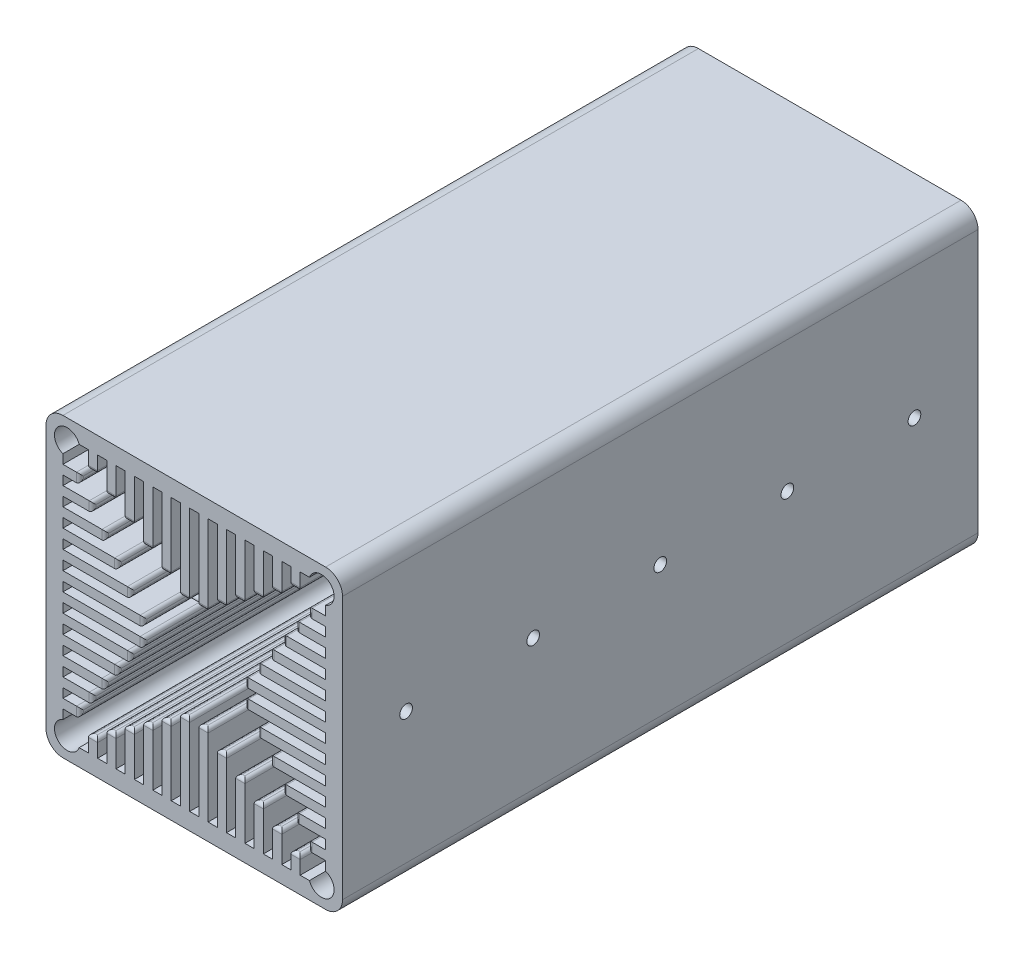
SolidWorks part; units mm, degrees
ref_plane "Front Plane" through (0, 0, 0) normal (0, 0, 1) x (1, 0, 0)
ref_plane "Top Plane" through (0, 0, 0) normal (0, 1, 0) x (1, 0, 0)
ref_plane "Right Plane" through (0, 0, 0) normal (1, 0, 0) x (0, 0, -1)
sketch "Sketch1" plane through (0, 0, 0) normal (0, 0, 1) x (1, 0, 0)
  line L1 (0, 0) -> (70, 0)
  line L2 (0, 0) -> (0, -70)
  line L3 (0, -70) -> (70, -70)
  line L4 (70, 0) -> (70, -70)
  dimension "D1" = 70
  dimension "D2" = 70
extrude "Boss-Extrude1" add sketch "Sketch1" along normal blind 150
fillet "Fillet1" radius 4 4 edges at (0, -70, 75) (70, -70, 75) (70, 0, 75) (0, 0, 75)
sketch "Sketch2" plane through (0, 0, 150) normal (0, 0, 1) x (1, 0, 0)
  line L0 (7.8261, -66) -> (10, -66)
  line L1 (10, -66) -> (10, -62)
  line L2 (10, -62) -> (12.1739, -62)
  line L3 (12.1739, -62) -> (12.1739, -66)
  line L4 (12.1739, -66) -> (14.3478, -66)
  line L5 (14.3478, -66) -> (14.3478, -59)
  line L6 (14.3478, -59) -> (16.5217, -59)
  line L7 (16.5217, -59) -> (16.5217, -66)
  line L8 (16.5217, -66) -> (18.6957, -66)
  line L9 (18.6957, -66) -> (18.6957, -56)
  line L10 (18.6957, -56) -> (20.8696, -56)
  line L11 (20.8696, -56) -> (20.8696, -66)
  line L12 (20.8696, -66) -> (23.0435, -66)
  line L13 (23.0435, -66) -> (23.0435, -53)
  line L14 (23.0435, -53) -> (25.2174, -53)
  line L15 (25.2174, -53) -> (25.2174, -66)
  line L16 (25.2174, -66) -> (27.3913, -66)
  line L17 (27.3913, -66) -> (27.3913, -50)
  line L18 (27.3913, -50) -> (29.5652, -50)
  line L19 (29.5652, -50) -> (29.5652, -66)
  line L20 (29.5652, -66) -> (31.7391, -66)
  line L21 (31.7391, -66) -> (31.7391, -47)
  line L22 (31.7391, -47) -> (33.913, -47)
  line L23 (33.913, -47) -> (33.913, -66)
  line L24 (33.913, -66) -> (36.087, -66)
  line L25 (4, -70) -> (66, -70) construction
  line L26 (7.8261, -66) -> (1.1716, -68.8284) construction
  line L27 (62.1739, -66) -> (68.8284, -68.8284) construction
  line L28 (66, -62.1739) -> (66, -60)
  line L29 (66, -60) -> (62, -60)
  line L30 (62, -60) -> (62, -57.8261)
  line L31 (62, -57.8261) -> (66, -57.8261)
  line L32 (66, -57.8261) -> (66, -55.6522)
  line L33 (66, -55.6522) -> (59, -55.6522)
  line L34 (59, -55.6522) -> (59, -53.4783)
  line L35 (59, -53.4783) -> (66, -53.4783)
  line L36 (66, -53.4783) -> (66, -51.3043)
  line L37 (66, -51.3043) -> (56, -51.3043)
  line L38 (56, -51.3043) -> (56, -49.1304)
  line L39 (56, -49.1304) -> (66, -49.1304)
  line L40 (66, -49.1304) -> (66, -46.9565)
  line L41 (66, -46.9565) -> (53, -46.9565)
  line L42 (53, -46.9565) -> (53, -44.7826)
  line L43 (53, -44.7826) -> (66, -44.7826)
  line L44 (66, -44.7826) -> (66, -42.6087)
  line L45 (66, -42.6087) -> (50, -42.6087)
  line L46 (50, -42.6087) -> (50, -40.4348)
  line L47 (50, -40.4348) -> (66, -40.4348)
  line L48 (66, -40.4348) -> (66, -38.2609)
  line L49 (66, -38.2609) -> (47, -38.2609)
  line L50 (36.087, -47) -> (36.087, -66)
  line L51 (38.2609, -47) -> (36.087, -47)
  line L52 (38.2609, -66) -> (38.2609, -47)
  line L53 (40.4348, -66) -> (38.2609, -66)
  line L54 (40.4348, -50) -> (40.4348, -66)
  line L55 (42.6087, -50) -> (40.4348, -50)
  line L56 (42.6087, -66) -> (42.6087, -50)
  line L57 (44.7826, -66) -> (42.6087, -66)
  line L58 (44.7826, -53) -> (44.7826, -66)
  line L59 (46.9565, -53) -> (44.7826, -53)
  line L60 (46.9565, -66) -> (46.9565, -53)
  line L61 (49.1304, -66) -> (46.9565, -66)
  line L62 (49.1304, -56) -> (49.1304, -66)
  line L63 (51.3043, -56) -> (49.1304, -56)
  line L64 (51.3043, -66) -> (51.3043, -56)
  line L65 (53.4783, -66) -> (51.3043, -66)
  line L66 (53.4783, -59) -> (53.4783, -66)
  line L67 (55.6522, -59) -> (53.4783, -59)
  line L68 (55.6522, -66) -> (55.6522, -59)
  line L69 (57.8261, -66) -> (55.6522, -66)
  line L70 (57.8261, -62) -> (57.8261, -66)
  line L71 (60, -62) -> (57.8261, -62)
  line L72 (60, -66) -> (60, -62)
  line L73 (62.1739, -66) -> (60, -66)
  line L74 (47, -38.2609) -> (47, -36.087)
  line L75 (47, -36.087) -> (66, -36.087)
  line L76 (66, -36.087) -> (66, -33.913)
  line L77 (66, -62.1739) -> (68.8284, -68.8284) construction
  line L78 (66, -7.8261) -> (68.8284, -1.1716) construction
  line L79 (47, -33.913) -> (66, -33.913)
  line L80 (47, -31.7391) -> (47, -33.913)
  line L81 (66, -31.7391) -> (47, -31.7391)
  line L82 (66, -29.5652) -> (66, -31.7391)
  line L83 (50, -29.5652) -> (66, -29.5652)
  line L84 (50, -27.3913) -> (50, -29.5652)
  line L85 (66, -27.3913) -> (50, -27.3913)
  line L86 (66, -25.2174) -> (66, -27.3913)
  line L87 (53, -25.2174) -> (66, -25.2174)
  line L88 (53, -23.0435) -> (53, -25.2174)
  line L89 (66, -23.0435) -> (53, -23.0435)
  line L90 (66, -20.8696) -> (66, -23.0435)
  line L91 (56, -20.8696) -> (66, -20.8696)
  line L92 (56, -18.6957) -> (56, -20.8696)
  line L93 (66, -18.6957) -> (56, -18.6957)
  line L94 (66, -16.5217) -> (66, -18.6957)
  line L95 (59, -16.5217) -> (66, -16.5217)
  line L96 (59, -14.3478) -> (59, -16.5217)
  line L97 (66, -14.3478) -> (59, -14.3478)
  line L98 (66, -12.1739) -> (66, -14.3478)
  line L99 (62, -12.1739) -> (66, -12.1739)
  line L100 (62, -10) -> (62, -12.1739)
  line L101 (66, -10) -> (62, -10)
  line L102 (66, -7.8261) -> (66, -10)
  line L103 (70, -66) -> (70, -4) construction
  line L104 (0, -4) -> (0, -66) construction
  line L105 (62.1739, -4) -> (60, -4)
  line L106 (60, -4) -> (60, -8)
  line L107 (60, -8) -> (57.8261, -8)
  line L108 (57.8261, -8) -> (57.8261, -4)
  line L109 (57.8261, -4) -> (55.6522, -4)
  line L110 (55.6522, -4) -> (55.6522, -11)
  line L111 (55.6522, -11) -> (53.4783, -11)
  line L112 (53.4783, -11) -> (53.4783, -4)
  line L113 (53.4783, -4) -> (51.3043, -4)
  line L114 (51.3043, -4) -> (51.3043, -14)
  line L115 (51.3043, -14) -> (49.1304, -14)
  line L116 (49.1304, -14) -> (49.1304, -4)
  line L117 (49.1304, -4) -> (46.9565, -4)
  line L118 (46.9565, -4) -> (46.9565, -17)
  line L119 (46.9565, -17) -> (44.7826, -17)
  line L120 (44.7826, -17) -> (44.7826, -4)
  line L121 (44.7826, -4) -> (42.6087, -4)
  line L122 (42.6087, -4) -> (42.6087, -20)
  line L123 (42.6087, -20) -> (40.4348, -20)
  line L124 (40.4348, -20) -> (40.4348, -4)
  line L125 (40.4348, -4) -> (38.2609, -4)
  line L126 (38.2609, -4) -> (38.2609, -23)
  line L127 (38.2609, -23) -> (36.087, -23)
  line L128 (36.087, -23) -> (36.087, -4)
  line L129 (36.087, -4) -> (33.913, -4)
  line L130 (62.1739, -4) -> (68.8284, -1.1716) construction
  line L131 (7.8261, -4) -> (1.1716, -1.1716) construction
  line L132 (4, -7.8261) -> (4, -10)
  line L133 (4, -10) -> (8, -10)
  line L134 (8, -10) -> (8, -12.1739)
  line L135 (8, -12.1739) -> (4, -12.1739)
  line L136 (4, -12.1739) -> (4, -14.3478)
  line L137 (4, -14.3478) -> (11, -14.3478)
  line L138 (11, -14.3478) -> (11, -16.5217)
  line L139 (11, -16.5217) -> (4, -16.5217)
  line L140 (4, -16.5217) -> (4, -18.6957)
  line L141 (4, -18.6957) -> (14, -18.6957)
  line L142 (14, -18.6957) -> (14, -20.8696)
  line L143 (14, -20.8696) -> (4, -20.8696)
  line L144 (4, -20.8696) -> (4, -23.0435)
  line L145 (4, -23.0435) -> (17, -23.0435)
  line L146 (17, -23.0435) -> (17, -25.2174)
  line L147 (17, -25.2174) -> (4, -25.2174)
  line L148 (4, -25.2174) -> (4, -27.3913)
  line L149 (4, -27.3913) -> (20, -27.3913)
  line L150 (20, -27.3913) -> (20, -29.5652)
  line L151 (20, -29.5652) -> (4, -29.5652)
  line L152 (4, -29.5652) -> (4, -31.7391)
  line L153 (4, -31.7391) -> (23, -31.7391)
  line L154 (33.913, -23) -> (33.913, -4)
  line L155 (31.7391, -23) -> (33.913, -23)
  line L156 (31.7391, -4) -> (31.7391, -23)
  line L157 (29.5652, -4) -> (31.7391, -4)
  line L158 (29.5652, -20) -> (29.5652, -4)
  line L159 (27.3913, -20) -> (29.5652, -20)
  line L160 (27.3913, -4) -> (27.3913, -20)
  line L161 (25.2174, -4) -> (27.3913, -4)
  line L162 (25.2174, -17) -> (25.2174, -4)
  line L163 (23.0435, -17) -> (25.2174, -17)
  line L164 (23.0435, -4) -> (23.0435, -17)
  line L165 (20.8696, -4) -> (23.0435, -4)
  line L166 (20.8696, -14) -> (20.8696, -4)
  line L167 (18.6957, -14) -> (20.8696, -14)
  line L168 (18.6957, -4) -> (18.6957, -14)
  line L169 (16.5217, -4) -> (18.6957, -4)
  line L170 (16.5217, -11) -> (16.5217, -4)
  line L171 (14.3478, -11) -> (16.5217, -11)
  line L172 (14.3478, -4) -> (14.3478, -11)
  line L173 (12.1739, -4) -> (14.3478, -4)
  line L174 (12.1739, -8) -> (12.1739, -4)
  line L175 (10, -8) -> (12.1739, -8)
  line L176 (10, -4) -> (10, -8)
  line L177 (7.8261, -4) -> (10, -4)
  line L178 (23, -31.7391) -> (23, -33.913)
  line L179 (23, -33.913) -> (4, -33.913)
  line L180 (4, -33.913) -> (4, -36.087)
  line L181 (4, -7.8261) -> (1.1716, -1.1716) construction
  line L182 (4, -62.1739) -> (1.1716, -68.8284) construction
  line L183 (23, -36.087) -> (4, -36.087)
  line L184 (23, -38.2609) -> (23, -36.087)
  line L185 (4, -38.2609) -> (23, -38.2609)
  line L186 (4, -40.4348) -> (4, -38.2609)
  line L187 (20, -40.4348) -> (4, -40.4348)
  line L188 (20, -42.6087) -> (20, -40.4348)
  line L189 (4, -42.6087) -> (20, -42.6087)
  line L190 (4, -44.7826) -> (4, -42.6087)
  line L191 (17, -44.7826) -> (4, -44.7826)
  line L192 (17, -46.9565) -> (17, -44.7826)
  line L193 (4, -46.9565) -> (17, -46.9565)
  line L194 (4, -49.1304) -> (4, -46.9565)
  line L195 (14, -49.1304) -> (4, -49.1304)
  line L196 (14, -51.3043) -> (14, -49.1304)
  line L197 (4, -51.3043) -> (14, -51.3043)
  line L198 (4, -53.4783) -> (4, -51.3043)
  line L199 (11, -53.4783) -> (4, -53.4783)
  line L200 (11, -55.6522) -> (11, -53.4783)
  line L201 (4, -55.6522) -> (11, -55.6522)
  line L202 (4, -57.8261) -> (4, -55.6522)
  line L203 (8, -57.8261) -> (4, -57.8261)
  line L204 (8, -60) -> (8, -57.8261)
  line L205 (4, -60) -> (8, -60)
  line L206 (4, -62.1739) -> (4, -60)
  line L207 (66, 0) -> (4, 0) construction
  arc A0 (0, -66) -> (4, -70) centre (4, -66) ccw construction
  arc A1 (66, -70) -> (70, -66) centre (66, -66) ccw construction
  arc A2 (70, -4) -> (66, 0) centre (66, -4) ccw construction
  arc A5 (4, 0) -> (0, -4) centre (4, -4) ccw construction
  arc A8 (4, -7.8261) -> (7.8261, -4) centre (4.9964, -4.9964) cw
  arc A9 (62.1739, -4) -> (66, -7.8261) centre (65.0036, -4.9964) cw
  arc A10 (66, -62.1739) -> (62.1739, -66) centre (65.0036, -65.0036) cw
  arc A11 (7.8261, -66) -> (4, -62.1739) centre (4.9964, -65.0036) cw
  point P184 (0, 0)
  point P223 (0, 0)
  point P224 (-42.6038, -51.3575)
  dimension "D17" = 4
  dimension "D28" = 8
  dimension "D31" = 3
  dimension "D32" = 3
  dimension "D33" = 3
  dimension "D34" = 3
  dimension "D1" = 4
  dimension "D2" = 4
  dimension "D3" = 3
  dimension "D4" = 3
  dimension "D5" = 3
  dimension "D6" = 3
  dimension "D7" = 3
  dimension "D8" = 10
  dimension "D9" = 8
  dimension "D10" = 3
  dimension "D11" = 3
  dimension "D12" = 3
  dimension "D13" = 3
  dimension "D14" = 3
  dimension "D15" = 4
  dimension "D16" = 8
  dimension "D18" = 3
  dimension "D19" = 3
  dimension "D20" = 3
  dimension "D21" = 3
  dimension "D22" = 3
  dimension "D23" = 3
  dimension "D24" = 3
  dimension "D25" = 3
  dimension "D26" = 3
  dimension "D27" = 3
  dimension "D29" = 8
  dimension "D30" = 4
extrude "Cut-Extrude1" cut sketch "Sketch2" against normal up to surface (150 mm away) up to face at (35, -35, 0)
fillet "Fillet2" radius 0.8 192 edges at (8, -60, 75) (8, -57.8261, 75) (11, -55.6522, 75) (11, -53.4783, 75) (14, -49.1304, 75) (14, -51.3043, 75) (17, -44.7826, 75) (17, -46.9565, 75) (20, -40.4348, 75) (20, -42.6087, 75) (8, -10, 75) (8, -12.1739, 75) (11, -16.5217, 75) (11, -14.3478, 75) (14, -20.8696, 75) (14, -18.6957, 75) (17, -25.2174, 75) (17, -23.0435, 75) (20, -27.3913, 75) (20, -29.5652, 75) (23, -33.913, 75) (23, -31.7391, 75) (23, -36.087, 75) (23, -38.2609, 75) (14.3478, -59, 75) (15.4348, -59, 0) (16.5217, -59, 75) (15.4348, -59, 150) (10, -62, 75) (11.087, -62, 0) (12.1739, -62, 75) (11.087, -62, 150) (18.6957, -56, 75) (19.7826, -56, 0) (20.8696, -56, 75) (19.7826, -56, 150) (23.0435, -53, 75) (24.1304, -53, 0) (25.2174, -53, 75) (24.1304, -53, 150) (27.3913, -50, 75) (28.4783, -50, 0) (29.5652, -50, 75) (28.4783, -50, 150) (31.7391, -47, 75) (32.8261, -47, 0) (33.913, -47, 75) (32.8261, -47, 150) (36.087, -47, 75) (37.1739, -47, 0) (38.2609, -47, 75) (37.1739, -47, 150) (40.4348, -50, 75) (41.5217, -50, 0) (42.6087, -50, 75) (41.5217, -50, 150) (44.7826, -53, 75) (45.8696, -53, 0) (46.9565, -53, 75) (45.8696, -53, 150) (49.1304, -56, 75) (50.2174, -56, 0) (51.3043, -56, 75) (50.2174, -56, 150) (53.4783, -59, 75) (54.5652, -59, 0) (55.6522, -59, 75) (54.5652, -59, 150) (57.8261, -62, 75) (58.913, -62, 0) (60, -62, 75) (58.913, -62, 150) (62, -60, 75) (62, -58.913, 0) (62, -57.8261, 75) (62, -58.913, 150) (59, -55.6522, 75) (59, -54.5652, 0) (59, -53.4783, 75) (59, -54.5652, 150) (56, -51.3043, 75) (56, -50.2174, 0) (56, -49.1304, 75) (56, -50.2174, 150) (50, -42.6087, 75) (50, -41.5217, 0) (50, -40.4348, 75) (50, -41.5217, 150) (53, -46.9565, 75) (53, -45.8696, 0) (53, -44.7826, 75) (53, -45.8696, 150) (47, -38.2609, 75) (47, -37.1739, 0) (47, -36.087, 75) (47, -37.1739, 150) (47, -33.913, 75) (47, -32.8261, 0) (47, -31.7391, 75) (47, -32.8261, 150) (50, -29.5652, 75) (50, -28.4783, 0) (50, -27.3913, 75) (50, -28.4783, 150) (53, -25.2174, 75) (53, -24.1304, 0) (53, -23.0435, 75) (53, -24.1304, 150) (56, -20.8696, 75) (56, -19.7826, 0) (56, -18.6957, 75) (56, -19.7826, 150) (59, -16.5217, 75) (59, -15.4348, 0) (59, -14.3478, 75) (59, -15.4348, 150) (62, -12.1739, 75) (62, -11.087, 0) (62, -10, 75) (62, -11.087, 150) (60, -8, 75) (58.913, -8, 0) (57.8261, -8, 75) (58.913, -8, 150) (55.6522, -11, 75) (54.5652, -11, 0) (53.4783, -11, 75) (54.5652, -11, 150) (51.3043, -14, 75) (50.2174, -14, 0) (49.1304, -14, 75) (50.2174, -14, 150) (46.9565, -17, 75) (45.8696, -17, 0) (44.7826, -17, 75) (45.8696, -17, 150) (40.4348, -20, 75) (42.6087, -20, 75) (38.2609, -23, 75) (36.087, -23, 75) (33.913, -23, 75) (31.7391, -23, 75) (29.5652, -20, 75) (27.3913, -20, 75) (25.2174, -17, 75) (23.0435, -17, 75) (20.8696, -14, 75) (18.6957, -14, 75) (16.5217, -11, 75) (14.3478, -11, 75) (12.1739, -8, 75) (10, -8, 75) (41.5217, -20, 0) (41.5217, -20, 150) (37.1739, -23, 0) (37.1739, -23, 150) (32.8261, -23, 0) (32.8261, -23, 150) (28.4783, -20, 0) (28.4783, -20, 150) (24.1304, -17, 0) (24.1304, -17, 150) (19.7826, -14, 0) (19.7826, -14, 150) (15.4348, -11, 0) (15.4348, -11, 150) (11.087, -8, 0) (11.087, -8, 150) (8, -11.087, 0) (8, -11.087, 150) (11, -15.4348, 0) (11, -15.4348, 150) (14, -19.7826, 0) (14, -19.7826, 150) (17, -24.1304, 0) (17, -24.1304, 150) (20, -28.4783, 0) (20, -28.4783, 150) (23, -32.8261, 0) (23, -32.8261, 150) (23, -37.1739, 0) (23, -37.1739, 150) (20, -41.5217, 0) (20, -41.5217, 150) (17, -45.8696, 0) (17, -45.8696, 150) (14, -50.2174, 0) (14, -50.2174, 150) (11, -54.5652, 0) (11, -54.5652, 150) (8, -58.913, 0) (8, -58.913, 150)
sketch "Sketch3" plane through (70, 0, 0) normal (1, 0, 0) x (0, 0, -1)
  line L0 (-135, -35) -> (-135, -4) construction
  line L1 (0, -4) -> (-150, -4) construction
  line L2 (-135, -35) -> (-135, -66) construction
  line L3 (-150, -66) -> (0, -66) construction
  line L4 (-150, -66) -> (-150, -4) construction
  circle A0 centre (-135, -35) radius 1.5
  circle A1 centre (-105, -35) radius 1.5
  circle A2 centre (-75, -35) radius 1.5
  circle A3 centre (-45, -35) radius 1.5
  circle A4 centre (-15, -35) radius 1.5
  dimension "D2" = 3
  dimension "D1" = 15
  dimension "D4" = 45
  dimension "D3" = 5
extrude "Cut-Extrude2" cut sketch "Sketch3" against normal up to surface (70 mm away) up to face at (0, -35, 75)
